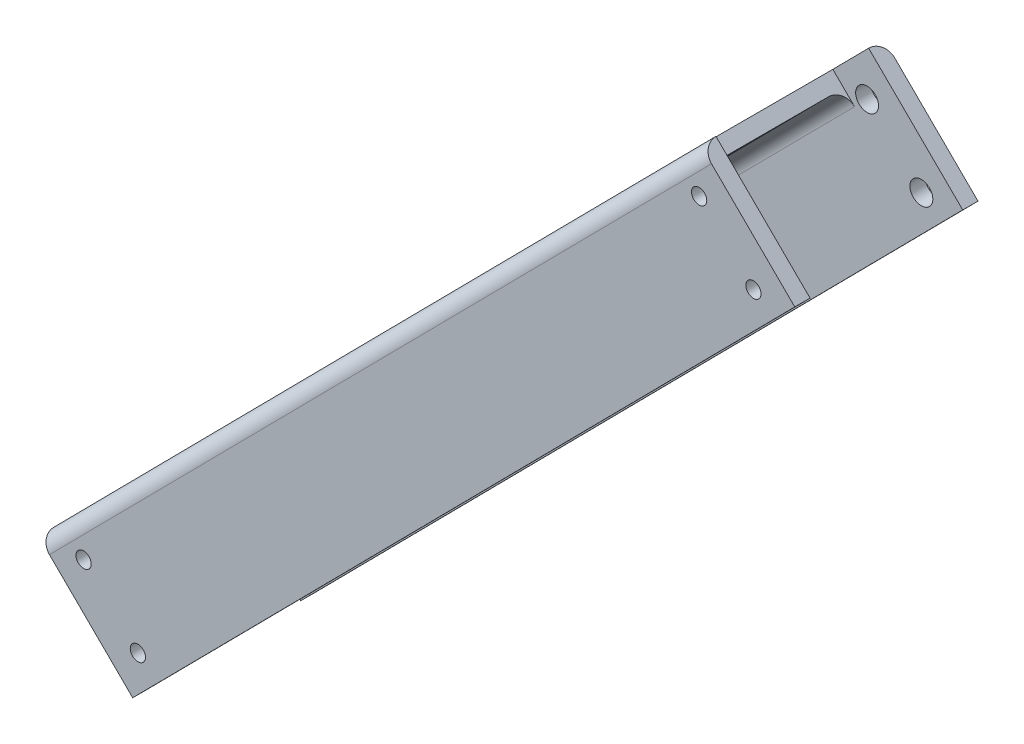
SolidWorks part; units mm, degrees
ref_plane "Front Plane" through (0, 0, 0) normal (0, 0, 1) x (1, 0, 0)
ref_plane "Top Plane" through (0, 0, 0) normal (0, 1, 0) x (1, 0, 0)
ref_plane "Right Plane" through (0, 0, 0) normal (1, 0, 0) x (0, 0, -1)
sketch "Sketch2" plane through (0, 0, 0) normal (0, 0, 1) x (1, 0, 0)
  line L0 (165.715, 148.457) -> (35.6364, 16.9102)
  line L1 (35.6364, 16.9102) -> (54.1241, -1.3711)
  line L4 (54.1241, -1.3711) -> (184.2027, 130.1757)
  line L25 (165.715, 148.457) -> (184.2027, 130.1757)
extrude "Boss-Extrude1" add sketch "Sketch2" against normal blind 3
sketch "Sketch4" plane through (0, 0, -36) normal (0, 0, -1) x (-1, 0, 0)
  line L6 (-165.715, 148.457) -> (-184.2027, 130.1757)
  line L9 (-184.2027, 130.1757) -> (-54.1241, -1.3711)
  line L10 (-54.1241, -1.3711) -> (-35.6364, 16.9102)
  line L11 (-35.6364, 16.9102) -> (-165.715, 148.457)
  line L12 (-165.715, 148.457) -> (-184.2027, 130.1757)
  line L15 (-184.2027, 130.1757) -> (-54.1241, -1.3711)
  line L16 (-54.1241, -1.3711) -> (-35.6364, 16.9102)
  line L17 (-35.6364, 16.9102) -> (-165.715, 148.457)
  dimension "D1" = 0
extrude "Boss-Extrude2" add sketch "Sketch4" against normal blind 3 separate body
sketch "Sketch5" plane through (0, 0, -3) normal (0, 0, -1) x (-1, 0, 0)
  line L0 (-35.6364, 16.9102) -> (-165.715, 148.457) construction
  line L1 (-35.6364, 16.9102) -> (-165.715, 148.457)
  line L2 (-37.7696, 14.8008) -> (-167.8482, 146.3476)
  line L3 (-37.7696, 14.8008) -> (-35.6364, 16.9102)
  line L4 (-167.8482, 146.3476) -> (-165.715, 148.457)
  dimension "D1" = 3
extrude "Boss-Extrude3" add sketch "Sketch5" along normal up to surface (30 mm away) up to face at (109.9195, 73.543, -33)
fillet "Fillet1" radius 3 4 edges at (102.8089, 80.5742, -3) (102.8089, 80.5742, -33) (100.6757, 82.6836, -36) (100.6757, 82.6836, 0)
sketch "Sketch6" plane through (9.5636, -9.4569, 0) normal (-0.7111, 0.7031, 0) x (0, 0, 1)
  circle A0 centre (-18, 197.0812) radius 7.5
extrude "Cut-Extrude1" cut sketch "Sketch6" against normal up to surface (3 mm away) up to face at (102.8089, 80.5742, -18)
sketch "Sketch7" plane through (9.5636, -9.4569, 0) normal (-0.7111, 0.7031, 0) x (0, 0, 1)
  line L5 (-3, 37.0812) -> (-3, 222.0812) construction
  line L6 (-3, 212.0812) -> (-3, 222.0812)
  line L7 (-33, 222.0812) -> (-33, 37.0812) construction
  line L8 (-33, 222.0812) -> (-33, 212.0812)
  line L9 (-33, 212.0812) -> (-3, 212.0812)
  line L12 (-33, 222.0812) -> (-3, 222.0812)
  line L13 (-36, 129.5812) -> (0, 129.5812) construction
  line L14 (-36, 37.0812) -> (-36, 222.0812) construction
  line L15 (0, 222.0812) -> (0, 37.0812) construction
  line L16 (-33, 37.0812) -> (-3, 37.0812)
  line L17 (-33, 47.0812) -> (-3, 47.0812)
  line L18 (-33, 37.0812) -> (-33, 47.0812)
  line L19 (-3, 47.0812) -> (-3, 37.0812)
extrude "Cut-Extrude2" cut sketch "Sketch7" against normal up to surface (26 mm away) up to face at (119.1634, 64.4023, -1.5)
sketch "Sketch8" plane through (0, 0, 0) normal (0, 0, 1) x (1, 0, 0)
  line L0 (58.6944, 3.2508) -> (40.2067, 21.5321) construction
  line L5 (179.6323, 125.5538) -> (161.1447, 143.8351) construction
  line L6 (158.6837, 141.3464) -> (165.715, 148.457) construction
  line L8 (100.6757, 82.6836) -> (119.1634, 64.4023) construction
  line L9 (42.6677, 24.0208) -> (158.6837, 141.3464) construction
  line L10 (54.1241, -1.3711) -> (184.2027, 130.1757) construction
  circle A0 centre (176.077, 129.0694) radius 1.5
  circle A1 centre (165.4111, 139.6163) radius 1.5
  circle A2 centre (44.4731, 17.3134) radius 1.5
  circle A3 centre (55.1391, 6.7664) radius 1.5
extrude "Cut-Extrude3" cut sketch "Sketch8" against normal blind 3
sketch "Sketch9" plane through (0, 0, -36) normal (0, 0, -1) x (-1, 0, 0)
  circle A0 centre (-165.4111, 139.6163) radius 2.25
  circle A1 centre (-176.077, 129.0694) radius 2.25
  circle A2 centre (-44.4731, 17.3134) radius 2.25
  circle A3 centre (-55.1391, 6.7664) radius 2.25
extrude "Cut-Extrude4" cut sketch "Sketch9" against normal blind 3
fillet "Fillet2" radius 1 2 edges at (142.8634, 125.3474, -18) (144.9966, 123.2381, -18)
